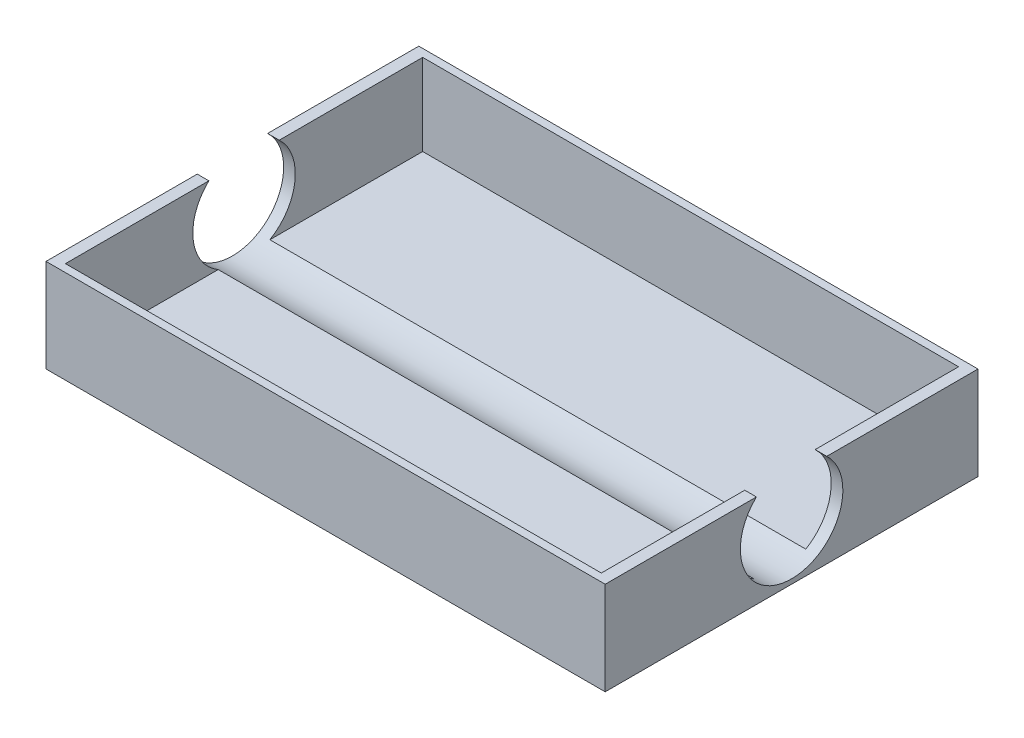
SolidWorks part; units mm, degrees
ref_plane "Front Plane" through (0, 0, 0) normal (0, 0, 1) x (1, 0, 0)
ref_plane "Top Plane" through (0, 0, 0) normal (0, 1, 0) x (1, 0, 0)
ref_plane "Right Plane" through (0, 0, 0) normal (1, 0, 0) x (0, 0, -1)
sketch "Sketch1" plane through (0, 0, 0) normal (0, 1, 0) x (1, 0, 0)
  line L1 (-60, -40) -> (60, -40)
  line L2 (-60, -40) -> (-60, 40)
  line L3 (-60, 40) -> (60, 40)
  line L4 (60, -40) -> (60, 40)
  line L5 (-60, -40) -> (60, 40) construction
  line L6 (-60, 40) -> (60, -40) construction
  line L11 (57.5, 38.3333) -> (-57.5, 38.3333)
  line L12 (57.5, 38.3333) -> (57.5, -38.3333)
  line L13 (57.5, -38.3333) -> (-57.5, -38.3333)
  line L14 (-57.5, 38.3333) -> (-57.5, -38.3333)
  line L15 (57.5, 38.3333) -> (-57.5, -38.3333) construction
  line L16 (57.5, -38.3333) -> (-57.5, 38.3333) construction
  point P0 (0, 0)
  point P6 (0, 0)
  dimension "D1" = 120
  dimension "D2" = 80
  dimension "D3" = 2.5
extrude "Boss-Extrude1" add sketch "Sketch1" along normal blind 20
extrude "Boss-Extrude2" add sketch "Sketch1<3>" along normal blind 2.5 contours L11 L14 L13 L12 region at (0, 0, 0)
sketch "Sketch1<3>" plane through (0, 0, 0) normal (0, 1, 0) x (1, 0, 0) same geometry as "Sketch1"
sketch "Sketch2" plane through (-60, 0, 0) normal (-1, 0, 0) x (0, 0, 1)
  line L1 (-40, 0) -> (40, 0) construction
  circle A0 centre (0, 12) radius 11
  point P2 (0, 13.5991)
  dimension "D1" = 22
  dimension "D2" = 1
extrude "Cut-Extrude1" cut sketch "Sketch2" against normal through all
